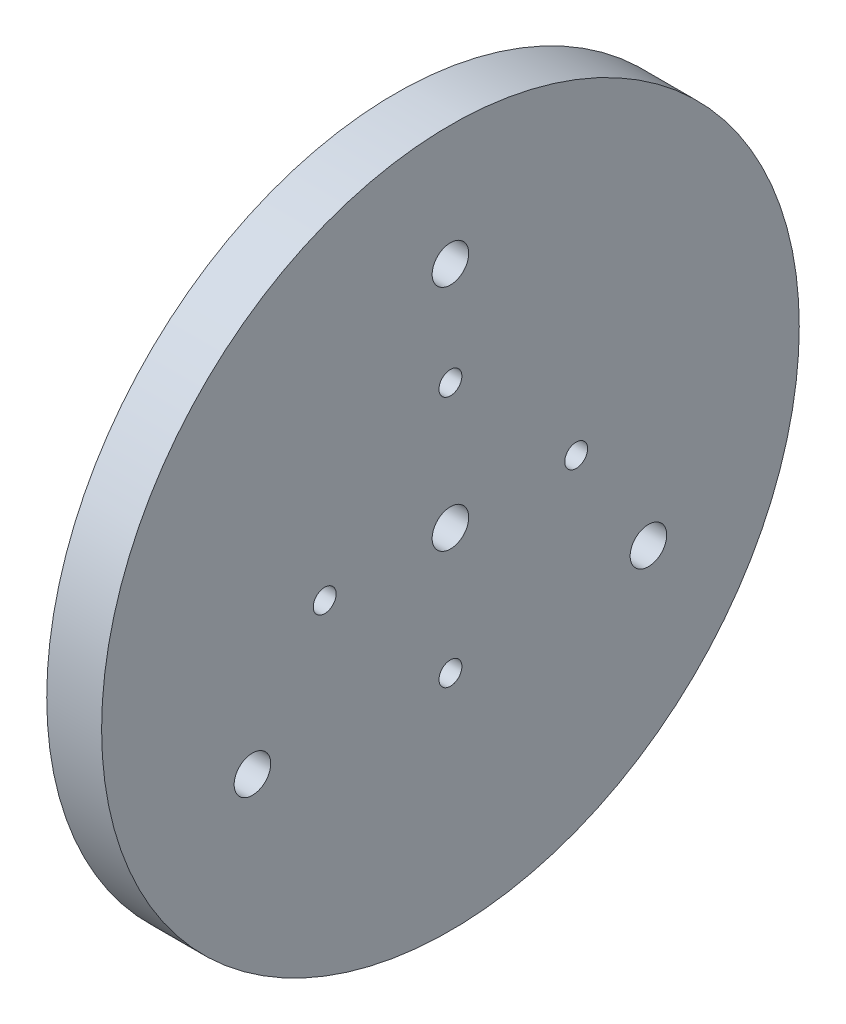
SolidWorks part; units mm, degrees
ref_plane "Front Plane" through (0, 0, 0) normal (0, 0, 1) x (1, 0, 0)
ref_plane "Top Plane" through (0, 0, 0) normal (0, 1, 0) x (1, 0, 0)
ref_plane "Right Plane" through (0, 0, 0) normal (1, 0, 0) x (0, 0, -1)
sketch "Sketch2" plane through (0, 0, 0) normal (1, 0, 0) x (0, 0, -1)
  line L0 (0, 76.29) -> (0, -76.29) construction
  line L1 (-76.29, 0) -> (79.9536, 0) construction
  circle A0 centre (0, 0) radius 76.29
  circle A1 centre (0, 27.5) radius 2.5
  circle A2 centre (27.5, 0) radius 2.5
  circle A3 centre (0, -27.5) radius 2.5
  circle A4 centre (-27.5, 0) radius 2.5
  circle A5 centre (0, 50) radius 4
  circle A6 centre (43.3013, -25) radius 4
  circle A7 centre (-43.3013, -25) radius 4
  circle A8 centre (0, 0) radius 4
  circle A9 centre (0, 0) radius 22.5 construction
  point P18 (0, 0)
  point P24 (0, 0)
  dimension "D1" = 152.58
  dimension "D2" = 5
  dimension "D4" = 55
  dimension "D5" = 8
  dimension "D6" = 50
  dimension "D8" = 8
  dimension "D9" = 45
  dimension "D3" = 4
  dimension "D7" = 3
extrude "Boss-Extrude1" add sketch "Sketch2" along normal blind 12
